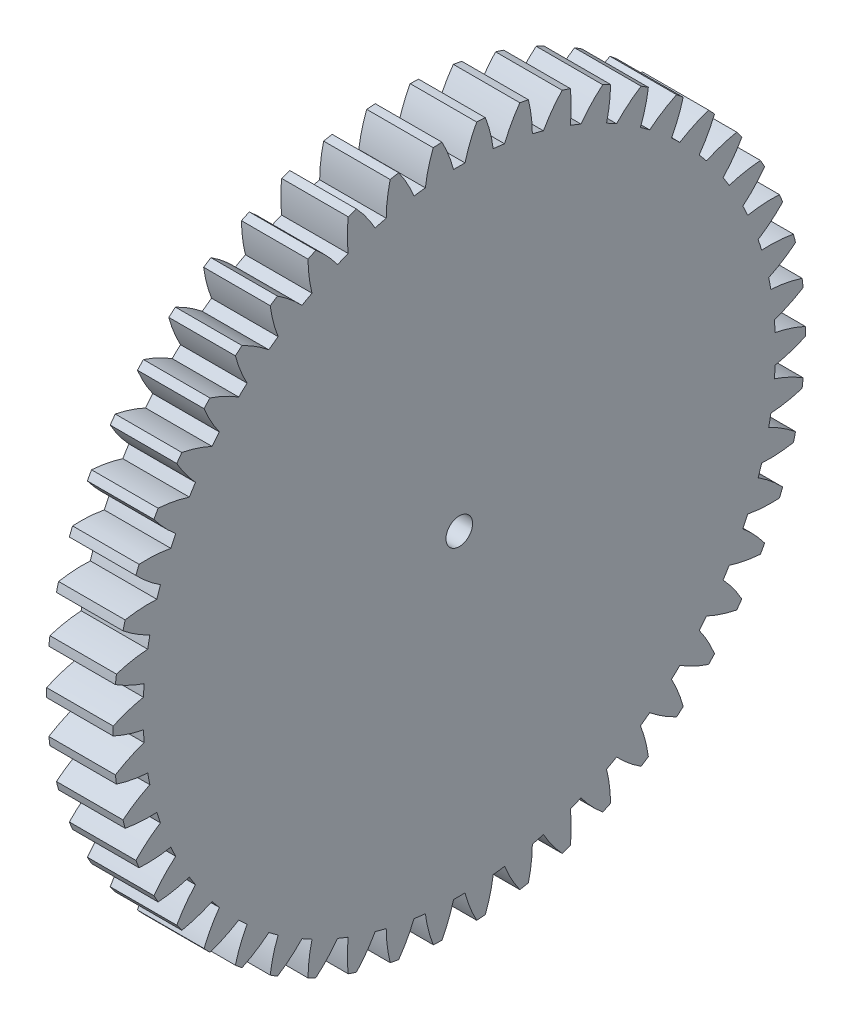
SolidWorks part; units mm, degrees
ref_plane "Plane1" through (0, 0, 0) normal (0, 0, 1) x (1, 0, 0)
ref_plane "Plane2" through (0, 0, 0) normal (0, 1, 0) x (1, 0, 0)
ref_plane "Plane3" through (0, 0, 0) normal (1, 0, 0) x (0, 0, -1)
sketch "HoldingSke" plane through (0, 0, 0) normal (0, 1, 0) x (1, 0, 0)
  line L0 (0, 0) -> (0.3214, -0.383)
  line L1 (-15, 0) -> (100, 0) construction
  line L2 (0, 0) -> (-2.1039, 2.3779)
  line L3 (0, 0) -> (-11.863, 4.5341)
  line L4 (0, 0) -> (5.5511, 6.6156)
  line L5 (0, 0) -> (-18.7391, -6.9891)
  line L6 (0, 0) -> (-8.2896, -5.593)
  line L7 (-2.1039, 2.3779) -> (2.2011, 21.9091)
  line L8 (-76.2, 54.61) -> (-75.5, 54.61)
  line L9 (-71.009, 38.7566) -> (-53.1078, 45.2721)
  line L10 (-76.2, 71.12) -> (104.1128, 71.12)
  line L11 (0, 0) -> (-10, 0)
  line L12 (-76.2, 101.6) -> (-76.133, 101.6)
  line L13 (24.9733, 27.94) -> (52.9518, 28.4284)
  line L14 (24.9733, 27.94) -> (24.9743, 27.94)
  line L15 (24.9733, 27.94) -> (100.4006, 29.5858)
  line L16 (-63.627, -2) -> (-12.827, -2)
  circle A0 centre (0, 0) radius 2
  circle A1 centre (0, 0) radius 25
  circle A2 centre (0, 0) radius 25
  circle A3 centre (0, 0) radius 2
  dimension "MHD" = 50
  dimension "Hub_dia" = 50
  dimension "Bore" = 4
  dimension "MBD" = 4
  dimension "Num_teeth" = 50
  dimension "Pitch_radius" = 180.3128
  dimension "Pitch" = 0.5
  dimension "Width" = 10
  dimension "Overall_len" = 20
  dimension "Show_teeth" = 50
  dimension "Thickness" = 10
  dimension "OAL" = 20.0001
  dimension "T_dim" = 0.7
  dimension "Ap" = 20
  dimension "H" = 19.05
  dimension "Backlash" = 0.067
  dimension "Addendum_fac" = 1
  dimension "Dedendum_fac" = 1.25
  dimension "Clearance_fac" = 0.25
  dimension "Dedendum_add" = 0.001
  dimension "Module" = 2
sketch "BasProSke" plane through (0, 0, 0) normal (0, 1, 0) x (1, 0, 0)
  line L0 (-10, 0) -> (60, 0) construction
  line L1 (0, 0) -> (0, 52)
  line L2 (0, 0) -> (10, 0)
  line L3 (10, 0) -> (10, 52)
  line L4 (10, 52) -> (0, 52)
  dimension "Diameter" = 104
  dimension "Thickness" = 10
revolve "Base-Revolve" add sketch "BasProSke" angle 360 about L0
sketch "TooCutSke" plane through (0, 0, 0) normal (1, 0, 0) x (0, 0, -1)
  line L1 (0, 0) -> (0, 107) construction
  line L2 (0, 0) -> (-1.6878, 49.9715) construction
  line L3 (0, 0) -> (-6.2764, 99.7605) construction
  line L4 (-1.6878, 49.9715) -> (-3.1382, 49.8803) construction
  arc A0 (0.8606, 47.4912) -> (-0.8606, 47.4912) centre (0, 0) ccw
  arc A1 (2.629, 51.9589) -> (-2.629, 51.9589) centre (0, 0) ccw
  circle A2 centre (0, 0) radius 50 construction
  circle A3 centre (0, 0) radius 46.9846 construction
  arc A4 (-0.8606, 47.4912) -> (-2.629, 51.9589) centre (-20.2064, 42.4176) ccw
  arc A5 (2.629, 51.9589) -> (0.8606, 47.4912) centre (20.2064, 42.4176) ccw
  dimension "Root_dia" = 94.998
  dimension "Overcut_dia" = 104.0508
  dimension "Pitch_dia" = 100
  dimension "Base_dia" = 93.9693
  dimension "Flank_rad" = 20
  dimension "Half_ang" = 3.6
  dimension "Half_CT" = 1.4533
extrude "ToothCut" cut sketch "TooCutSke" along normal through all
fillet "Breaks" [suppressed] radius 0.04 tangent propagation no
fillet "RootFillets" [suppressed] radius 0.501
pattern_circular "TeethCuts" count 50 every 7.2 about axis through (-10, 0, 0) along (1, 0, 0) of "ToothCut", "RootFillets", "Breaks"
sketch "HubNeaOneSke" plane through (0, 0, 0) normal (-1, 0, 0) x (0, 0, 1)
  circle A0 centre (0, 0) radius 25
  dimension "Diameter" = 50
extrude "HubNearOne" add sketch "HubNeaOneSke" along normal blind 10.0001
sketch "HubNeaBotSke" plane through (0, 0, 0) normal (-1, 0, 0) x (0, 0, 1)
  circle A0 centre (0, 0) radius 25
  dimension "Diameter" = 50
extrude "HubNearBoth" [suppressed] add sketch "HubNeaBotSke" along normal blind 5
ref_plane "FarPln" through (10, 0, 0) normal (1, 0, 0) x (0, 0, -1)
sketch "HubFarSke" plane through (10, 0, 0) normal (1, 0, 0) x (0, 0, -1)
  circle A0 centre (0, 0) radius 25
  dimension "Diameter" = 50
extrude "HubFar" [suppressed] add sketch "HubFarSke" along normal blind 5
sketch "BorSke" plane through (0, 0, 0) normal (1, 0, 0) x (0, 0, -1)
  circle A0 centre (0, 0) radius 2
  dimension "Diameter" = 4
extrude "Bore" cut sketch "BorSke" along normal mid plane 40.0001
sketch "KeySke" plane through (0, 0, 0) normal (1, 0, 0) x (0, 0, -1)
  line L0 (-0.8, 0) -> (-0.8, 2.7)
  line L1 (-0.8, 2.7) -> (0.8, 2.7)
  line L2 (0.8, 2.7) -> (0.8, 0)
  line L3 (0, 0) -> (0, 34) construction
  line L4 (-0.8, 0) -> (0.8, 0)
  dimension "Offset" = 2.7
  dimension "Width" = 1.6
extrude "Keyway" [suppressed] cut sketch "KeySke" along normal mid plane 40.0001
pattern_circular "Keyway2" [suppressed] count 2 every 90 about axis through (-10, 0, 0) along (1, 0, 0)
equation "' \"Module@HoldingSke\" = 6.35"
equation "' \"Num_teeth@HoldingSke\" = 12"
equation "' \"Ap@HoldingSke\" =  20"
equation "' \"Width@HoldingSke\" = 0.5 * 25.4"
equation "' \"Hub_dia@HoldingSke\"= 1 * 25.4"
equation "' \"Overall_len@HoldingSke\" = 1.0 * 25.4"
equation "' \"Bore@HoldingSke\" = 0.75 * 25.4"
equation "' \"T_dim@HoldingSke\" = 0.1 * 25.4"
equation "' \"Width@KeySke\" = 0.25 * 25.4"
equation "' \"Show_teeth@HoldingSke\" = 13"
equation "' \"Backlash@HoldingSke\" = 0.009 * 25.4"
equation "' \"Addendum_fac@HoldingSke\" = 1.0"
equation "' \"Dedendum_fac@HoldingSke\" = 1.25"
equation "' \"Dedendum_add@HoldingSke\" = 0.00005 * 25.4"
equation "' \"Clearance_fac@HoldingSke\" = 0.25"
equation "\"Pitch@HoldingSke\" = 1 / \"Module@HoldingSke\""
equation "\"Overcut_dia@TooCutSke\" = (\"Num_teeth@HoldingSke\" + 2 * \"Addendum_fac@HoldingSke\") / \"Pitch@HoldingSke\" + 0.002 * 25.4"
equation "\"Pitch_dia@TooCutSke\" = \"Num_teeth@HoldingSke\" / \"Pitch@HoldingSke\""
equation "\"Base_dia@TooCutSke\" = \"Num_teeth@HoldingSke\" / \"Pitch@HoldingSke\" * cos((\"Ap@HoldingSke\"  * 3.14159265 / 180))"
equation "\"Root_dia@TooCutSke\" = (\"Num_teeth@HoldingSke\" + 2) / \"Pitch@HoldingSke\" - 2 * (\"Addendum_fac@HoldingSke\" + \"Dedendum_fac@HoldingSke\") / \"Pitch@HoldingSke\" - \"Dedendum_add@HoldingSke\" * 2"
equation "\"Half_ang@TooCutSke\" = 180 / \"Num_teeth@HoldingSke\""
equation "\"Half_CT@TooCutSke\" = \"Num_teeth@HoldingSke\" / \"Pitch@HoldingSke\" * sin((3.14159265 / 2 / \"Num_teeth@HoldingSke\")) / 2 - 7 * \"Backlash@HoldingSke\" / 4"
equation "\"Flank_rad@TooCutSke\" = \"Num_teeth@HoldingSke\" / \"Pitch@HoldingSke\" / 5"
equation "\"Radius@RootFillets\" = \"Clearance_fac@HoldingSke\" / \"Pitch@HoldingSke\" + \"Dedendum_add@HoldingSke\""
equation "\"Break_rad@Breaks\" = 0.02 / \"Pitch@HoldingSke\""
equation "\"Thickness@HoldingSke\" = \"Width@HoldingSke\""
equation "\"OAL@HoldingSke\" = \"Thickness@HoldingSke\""
equation "\"MHD@HoldingSke\" = (\"Num_teeth@HoldingSke\" + 2) / \"Pitch@HoldingSke\" - 2 * (\"Addendum_fac@HoldingSke\" + \"Dedendum_fac@HoldingSke\")  / \"Pitch@HoldingSke\" - \"Dedendum_add@HoldingSke\" * 2"
equation "\"MBD@HoldingSke\" = (\"Num_teeth@HoldingSke\" + 2) / \"Pitch@HoldingSke\" - 2 * (\"Addendum_fac@HoldingSke\" + \"Dedendum_fac@HoldingSke\")  / \"Pitch@HoldingSke\" - \"Dedendum_add@HoldingSke\" * 2 - 0.002 * 25.4"
equation "\"MHD@HoldingSke\" = ((sgn( \"MHD@HoldingSke\" - \"Hub_dia@HoldingSke\" )-1)*( \"MHD@HoldingSke\" - \"Hub_dia@HoldingSke\" ))/-2+ \"Hub_dia@HoldingSke\""
equation "\"MBD@HoldingSke\" = ((sgn( \"MBD@HoldingSke\" - \"Bore@HoldingSke\" )-1)*( \"MBD@HoldingSke\" - \"Bore@HoldingSke\" ))/-2+ \"Bore@HoldingSke\""
equation "\"OAL@HoldingSke\" = ((sgn( \"OAL@HoldingSke\" - \"Overall_len@HoldingSke\" )+1)*( \"OAL@HoldingSke\" - \"Overall_len@HoldingSke\" ))/2 + \"Overall_len@HoldingSke\" + 0.000002 * 25.4"
equation "\"Num_teeth@TeethCuts\" = int( \"Show_teeth@HoldingSke\" ) + 1"
equation "\"Num_teeth@TeethCuts\" = ((sgn( \"Num_teeth@TeethCuts\" - \"Num_teeth@HoldingSke\" )-1)*( \"Num_teeth@TeethCuts\" - \"Num_teeth@HoldingSke\" ))/-2+ \"Num_teeth@HoldingSke\""
equation "\"Num_teeth@TeethCuts\" = ((sgn( \"Num_teeth@TeethCuts\" - 2.0)+1)*( \"Num_teeth@TeethCuts\" - 2.0))/2 +2.0"
equation "\"Angle@TeethCuts\" = 360.0 / \"Num_teeth@HoldingSke\""
equation "\"Diameter@BasProSke\" = (\"Num_teeth@HoldingSke\" + 2 * \"Addendum_fac@HoldingSke\") / \"Pitch@HoldingSke\""
equation "\"Thickness@BasProSke\"  = \"Thickness@HoldingSke\""
equation "' \"Fillet_rad@BasProSke\" =  \"Thickness@HoldingSke\" * 0.05"
equation "\"MHD@HoldingSke\" = ((sgn( \"MHD@HoldingSke\" - \"Root_dia@TooCutSke\" )-1)*( \"MHD@HoldingSke\" - \"Root_dia@TooCutSke\" ))/-2+ \"Root_dia@TooCutSke\""
equation "\"Diameter@HubNeaOneSke\" = \"MHD@HoldingSke\""
equation "\"Length@HubNearOne\" = \"OAL@HoldingSke\" - \"Thickness@BasProSke\""
equation "\"Diameter@HubNeaBotSke\" = \"MHD@HoldingSke\""
equation "\"Length@HubNearBoth\" = ( \"OAL@HoldingSke\" - \"Thickness@BasProSke\" ) / 2.0"
equation "\"Thickness@FarPln\" = \"Thickness@BasProSke\""
equation "\"Diameter@HubFarSke\" = \"MHD@HoldingSke\""
equation "\"Length@HubFar\" = ( \"OAL@HoldingSke\" - \"Thickness@BasProSke\" ) / 2.0"
equation "\"Diameter@BorSke\" = \"MBD@HoldingSke\""
equation "\"D1@Bore\" = \"OAL@HoldingSke\" * 2.0"
equation "\"D1@Keyway\" = \"OAL@HoldingSke\" * 2.0"
equation "\"Offset@KeySke\" = \"T_dim@HoldingSke\" + \"MBD@HoldingSke\" / 2.0"
